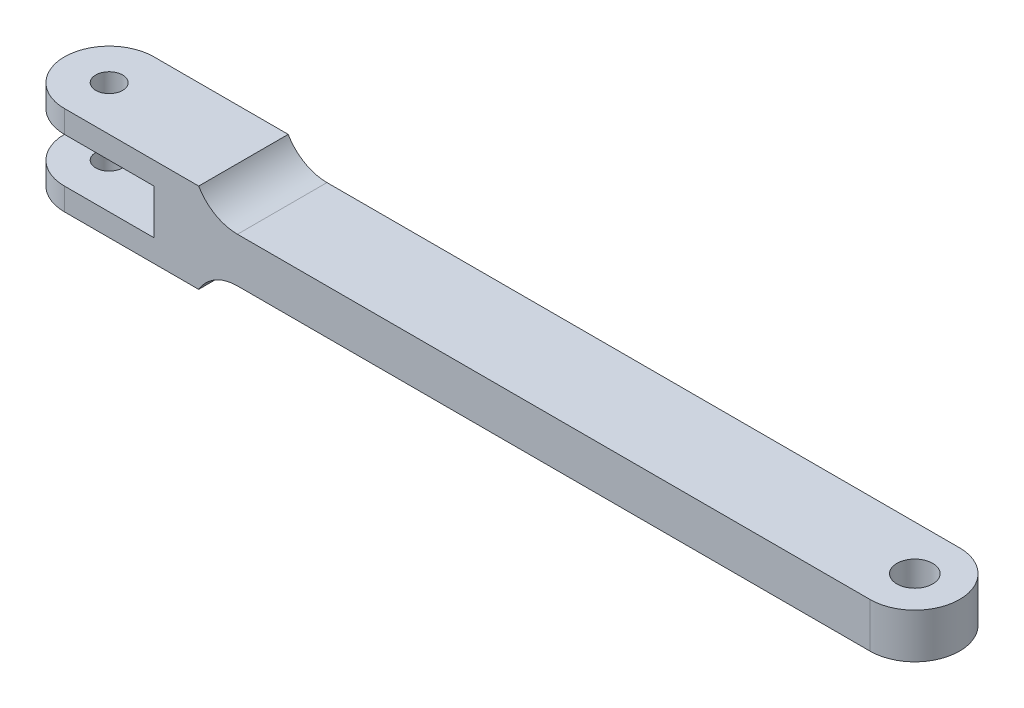
SolidWorks part; units mm, degrees
ref_plane "Alzado" through (0, 0, 0) normal (0, 0, 1) x (1, 0, 0)
ref_plane "Planta" through (0, 0, 0) normal (0, 1, 0) x (1, 0, 0)
ref_plane "Vista lateral" through (0, 0, 0) normal (1, 0, 0) x (0, 0, -1)
sketch "Croquis1" plane through (0, 0, 0) normal (0, 0, 1) x (1, 0, 0)
  line L1 (0, 0) -> (105, 0)
  line L2 (0, 0) -> (0, 2.5)
  line L3 (0, 10) -> (105, 10)
  line L5 (105, 2.5) -> (105, 0)
  line L7 (0, 7.5) -> (0, 10)
  line L9 (0, 7.5) -> (15, 7.5)
  line L12 (105, 7.5) -> (105, 10)
  line L13 (105, 7.5) -> (105, 2.5)
  line L14 (0, 2.5) -> (15, 2.5)
  line L15 (15, 7.5) -> (15, 2.5)
  dimension "D1" = 15
  dimension "D2" = 10
  dimension "D3" = 105
extrude "Saliente-Extruir1" add sketch "Croquis1" along normal blind 10
sketch "Croquis2" plane through (0, 10, 0) normal (0, 1, 0) x (1, 0, 0)
  line L1 (0, -10) -> (0, 0) construction
  line L3 (-4.0319, 0) -> (5, 0)
  line L4 (-4.0319, 0) -> (-4.0319, -10)
  line L5 (-4.0319, -10) -> (5, -10)
  circle A0 centre (5, -5) radius 1.5
  arc A2 (5, 0) -> (5, -10) centre (5, -5) ccw
  dimension "D1" = 3
  dimension "D2" = 5
extrude "Cortar-Extruir1" cut sketch "Croquis2" against normal blind 10
sketch "Croquis3" plane through (0, 10, 0) normal (0, 1, 0) x (1, 0, 0)
  line L0 (105, -5) -> (87.1029, -5) construction
  line L1 (105, -10) -> (105, 0) construction
  line L2 (105, 0) -> (5, 0) construction
  line L3 (90, 0) -> (105, 0)
  line L4 (90, 0) -> (90, -2.5)
  line L5 (90, -2.5) -> (105, -2.5)
  line L6 (105, 0) -> (105, -2.5)
  line L7 (105, -10) -> (105, -7.5)
  line L8 (90, -7.5) -> (105, -7.5)
  line L9 (90, -10) -> (90, -7.5)
  line L10 (90, -10) -> (105, -10)
  dimension "D1" = 15
  dimension "D2" = 2.5
extrude "Cortar-Extruir2" cut sketch "Croquis3" against normal blind 10
sketch "Croquis4" plane through (0, 0, 7.5) normal (0, 0, 1) x (1, 0, 0)
  line L0 (105, 0) -> (105, 10) construction
  line L1 (100, 10) -> (171.1124, 10)
  line L2 (171.1124, 10) -> (171.1124, 0)
  line L3 (171.1124, 0) -> (100, 0)
  line L4 (90, 0) -> (90, 10) construction
  circle A0 centre (100, 5) radius 1.5
  arc A1 (100, 0) -> (100, 10) centre (100, 5) ccw
  dimension "D2" = 10
  dimension "D3" = 3
  dimension "D1" = 5
  dimension "D4" = 81.1124
extrude "Cortar-Extruir3" cut sketch "Croquis4" against normal blind 10
sketch "Croquis8" plane through (0, 0, 7.5) normal (0, 0, 1) x (1, 0, 0)
  line L3 (90, 0) -> (100, 0)
  line L4 (100, 10) -> (90, 10)
  line L5 (90, 10) -> (90, 0)
  line L6 (90, 0) -> (100, 0)
  line L7 (100, 10) -> (90, 10)
  line L8 (90, 10) -> (90, 0)
  arc A1 (100, 0) -> (100, 10) centre (100, 5) ccw
  arc A2 (100, 0) -> (100, 10) centre (100, 5) ccw
  dimension "D1" = 0
extrude "Cortar-Extruir5" cut sketch "Croquis8" against normal blind 10
ref_plane "Plano1" through (0, 5, 0) normal (0, -1, 0) x (-1, 0, 0)
sketch "Croquis9" plane through (0, 5, 0) normal (0, -1, 0) x (-1, 0, 0)
  line L0 (-90, 0) -> (-90, -10) construction
  line L1 (-90, -10) -> (-95, -10)
  line L2 (-90, -10) -> (-90, 0)
  line L3 (-90, 0) -> (-95, 0)
  line L4 (-100, -5) -> (-100, 12.5399) construction
  circle A0 centre (-95, -5) radius 2
  arc A1 (-95, 0) -> (-95, -10) centre (-95, -5) ccw
  dimension "D2" = 4
  dimension "D1" = 100
extrude "Saliente-Extruir2" add sketch "Croquis9" along normal mid plane 5
sketch "Croquis10" plane through (0, 0, 0) normal (0, 0, -1) x (-1, 0, 0)
  line L0 (-85.2237, 5) -> (-14.8, 5) construction
  line L1 (-5.5, 5) -> (5.5, 5) construction
  line L3 (-100, 7.5) -> (-20, 7.5)
  line L4 (-100, 7.5) -> (-100, 24.1821)
  line L5 (-100, 24.1821) -> (-20, 24.1821)
  line L6 (-20, 7.5) -> (-20, 24.1821)
  line L7 (-100, 2.5) -> (-20, 2.5)
  line L8 (-100, 2.5) -> (-100, -13.4526)
  line L10 (-100, -13.4526) -> (-20, -13.4526)
  line L11 (-20, 2.5) -> (-20, -13.4526)
  dimension "D1" = 80
  dimension "D2" = 80
extrude "Cortar-Extruir6" cut sketch "Croquis10" against normal blind 10
fillet "Redondeo1" radius 5 2 edges at (20, 2.5, 5) (20, 7.5, 5)
